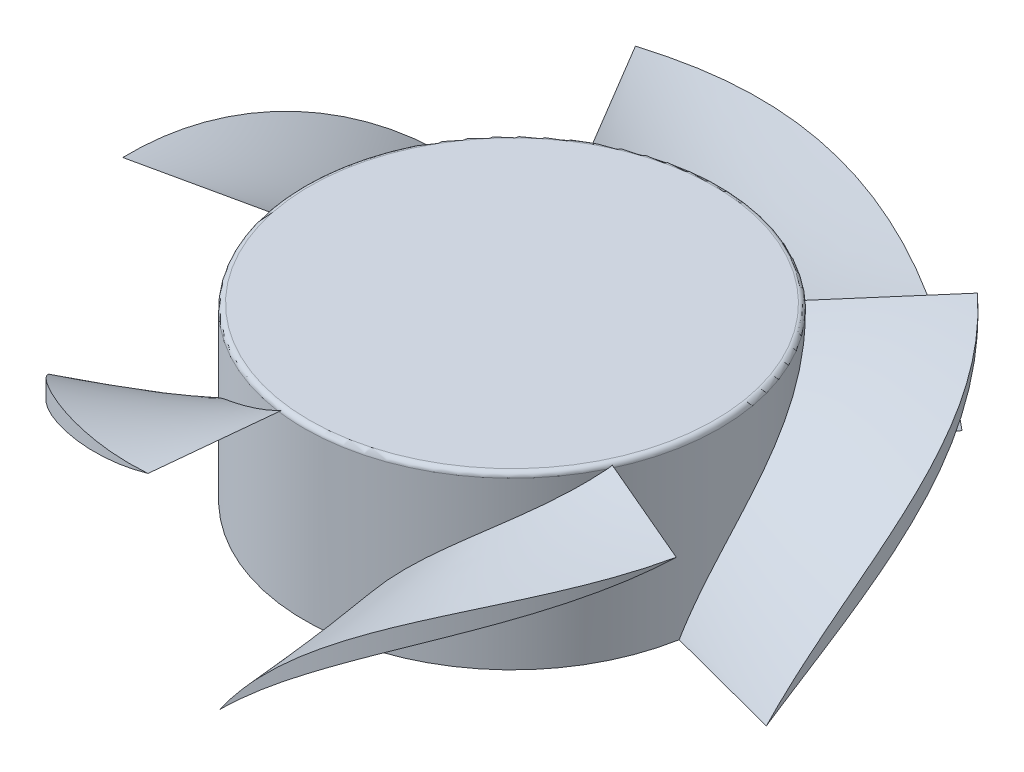
SolidWorks part; units mm, degrees
ref_plane "前基準面" through (0, 0, 0) normal (0, 0, 1) x (1, 0, 0)
ref_plane "上基準面" through (0, 0, 0) normal (0, 1, 0) x (1, 0, 0)
ref_plane "右基準面" through (0, 0, 0) normal (1, 0, 0) x (0, 0, -1)
sketch "Sketch1" plane through (0, 0, 0) normal (0, 1, 0) x (1, 0, 0)
  circle A0 centre (0, 0) radius 8.5
extrude "Boss-Extrude1" add sketch "Sketch1" along normal blind 7
sketch "Sketch2" plane through (0, 7, 0) normal (0, 1, 0) x (1, 0, 0)
  line L2 (-6.75, 11.6913) -> (0, 0)
  line L3 (0, 0) -> (6.75, 11.6913)
  line L4 (4.25, 7.3612) -> (-4.25, 7.3612) construction
  line L5 (6.75, 11.6913) -> (7.8903, 13.6664) construction
  line L6 (-6.75, 11.6913) -> (-7.9117, 13.7034) construction
  line L9 (0, 0) -> (-11.7052, 16.1108)
  line L10 (0, 0) -> (11.7052, 16.1108)
  line L11 (11.7052, 16.1108) -> (-11.7052, 16.1108)
  arc A0 (-6.75, 11.6913) -> (6.75, 11.6913) centre (0, 0) cw
  circle A3 centre (0, 0) radius 8.5 construction
  point P5 (0, 13.5)
  point P9 (0, 16.1108)
  point P12 (0, 7.3612)
  dimension "D2" = 13.5
  dimension "D1" = 60
  dimension "D3" = 72
ref_plane "Plane2" through (0, 0, -7.3612) normal (0, 0, 1) x (1, 0, 0)
sketch "Sketch3" plane through (0, 0, -7.3612) normal (0, 0, 1) x (1, 0, 0)
  line L0 (9.35, 0) -> (-9.35, 0) construction
  spline S0 degree 2 poles (-4.083, 6.89) (1.7455, 4.0431) (3.9464, 0) knots 0 0 0 1 1 1
  spline S1 degree 2 poles (3.9464, 0) (1.3357, 3.0793) (-4.083, 6.89) knots 0 0 0 1 1 1
  point P2 (4.25, 7)
  point P3 (-4.25, 7)
  dimension "D1" = 0.2
ref_plane "Plane1" through (0, 0, -13.5) normal (0, 0, 1) x (1, 0, 0)
sketch "Sketch4" plane through (0, 0, -13.5) normal (0, 0, 1) x (1, 0, 0)
  line L3 (9.35, 0) -> (-9.35, 0) construction
  spline S0 degree 2 poles (7.8903, 0) (2.4898, 6.0762) (-7.7231, 6.9333) knots 0 0 0 1 1 1
  spline S1 degree 2 poles (7.8903, 0) (1.7942, 4.7602) (-7.7231, 6.9333) knots 0 0 0 1 1 1
  point P5 (7.8903, 0)
  point P8 (-7.9117, 7)
  point P9 (7.8903, 7)
  dimension "D1" = 0.2
loft "Loft5" add profiles "Sketch4", "Sketch3"
extrude "Cut-Extrude1" cut sketch "Sketch2" against normal through all
pattern_circular "CirPattern1" count 5 every 72 about axis through (0, 7, 0) along (0, 1, 0) of "Loft5", "Cut-Extrude1"
fillet "Fillet1" radius 0.2 1 edges at (0, 7, 8.5)
